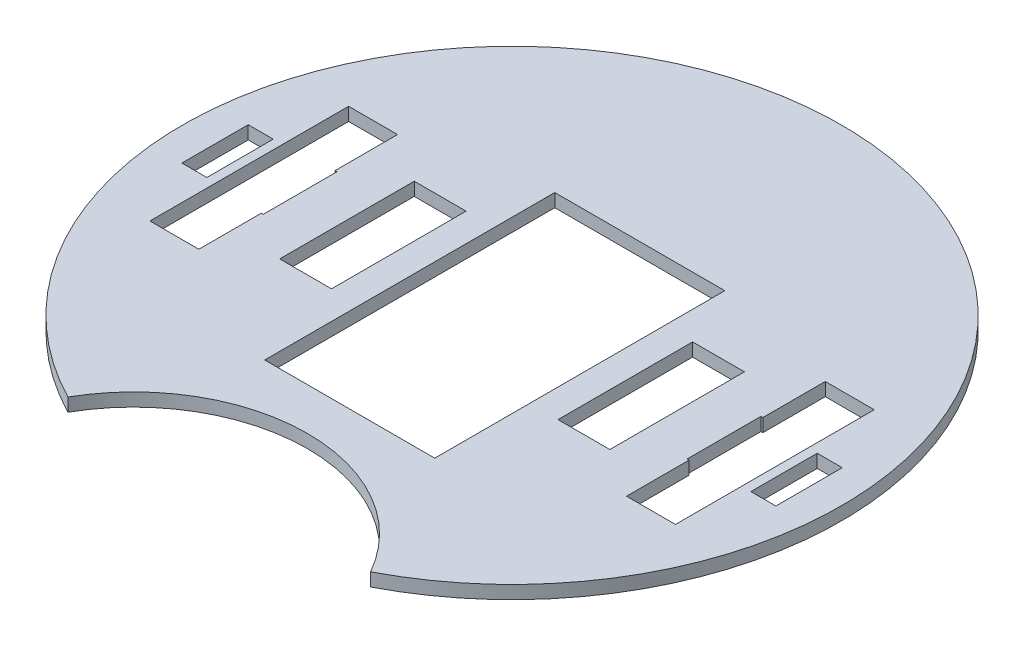
SolidWorks part; units mm, degrees
ref_plane "Front Plane" through (0, 0, 0) normal (0, 0, 1) x (1, 0, 0)
ref_plane "Top Plane" through (0, 0, 0) normal (0, 1, 0) x (1, 0, 0)
ref_plane "Right Plane" through (0, 0, 0) normal (1, 0, 0) x (0, 0, -1)
sketch "Sketch1" plane through (0, 0, 0) normal (0, 1, 0) x (1, 0, 0)
  line L0 (0, -83.2398) -> (-33.2911, -64.4046) construction
  line L1 (0, -83.2398) -> (0, 0) construction
  arc A0 (33.2911, -64.4046) -> (-33.2911, -64.4046) centre (0, 0) ccw
  arc A1 (33.2911, -64.4046) -> (-33.2911, -64.4046) centre (0, -83.2398) ccw
  dimension "D1" = 145
  dimension "D2" = 76.5
  dimension "D3" = 60.5
extrude "Boss-Extrude1" add sketch "Sketch1" along normal blind 2.9
sketch "solenoid placement" plane through (0, 2.9, 0) normal (0, 1, 0) x (1, 0, 0)
  line L0 (0, 0) -> (0, -36) construction
  line L1 (0, -36) -> (0, -44.9898) construction
  line L2 (-19, -36) -> (19, -36) construction
  line L3 (-19, -36) -> (-19, 28.4) construction
  line L4 (-19, 28.4) -> (19, 28.4) construction
  line L5 (19, -36) -> (19, 28.4) construction
  line L6 (-18.7, 28.1) -> (18.7, 28.1)
  line L7 (18.7, -35.7) -> (18.7, 28.1)
  line L8 (-18.7, -35.7) -> (18.7, -35.7)
  line L9 (-18.7, -35.7) -> (-18.7, 28.1)
  circle A1 centre (0, 0) radius 72.5 construction
  arc A2 (33.2911, -64.4046) -> (-33.2911, -64.4046) centre (0, 0) ccw construction
  arc A3 (33.2911, -64.4046) -> (-33.2911, -64.4046) centre (0, -83.2398) ccw construction
  dimension "D1" = 64.4
  dimension "D2" = 36
  dimension "D3" = 0.3
  dimension "D4" = 38
extrude "Cut-Extrude1" cut sketch "solenoid placement" against normal through all
sketch "Sketch2" plane through (0, 2.9, 0) normal (0, 1, 0) x (1, 0, 0)
  line L0 (47.34, -21.5538) -> (47.34, 21.5538) construction
  line L1 (-57.5, -21.5538) -> (-47.34, -21.5538) construction
  line L2 (-57.5, -21.5538) -> (-57.5, 21.5538) construction
  line L3 (-57.5, 21.5538) -> (-47.34, 21.5538) construction
  line L4 (-47.34, -21.5538) -> (-47.34, 21.5538) construction
  line L5 (57.5, 21.5538) -> (47.34, 21.5538) construction
  line L6 (57.5, -21.5538) -> (57.5, 21.5538) construction
  line L7 (57.5, -21.5538) -> (47.34, -21.5538) construction
  line L8 (57.8, -21.8538) -> (57.8, 21.8538)
  line L9 (57.8, -21.8538) -> (47.04, -21.8538)
  line L10 (47.04, -21.8538) -> (47.04, 21.8538)
  line L11 (57.8, 21.8538) -> (47.04, 21.8538)
  line L12 (0, 0) -> (0, 72.5) construction
  line L13 (-57.8, 21.8538) -> (-47.04, 21.8538)
  line L14 (-47.04, -21.8538) -> (-47.04, 21.8538)
  line L15 (-57.8, -21.8538) -> (-47.04, -21.8538)
  line L16 (-57.8, -21.8538) -> (-57.8, 21.8538)
  arc A0 (33.2911, -64.4046) -> (-33.2911, -64.4046) centre (0, 0) ccw construction
extrude "Cut-Extrude2" cut sketch "Sketch2" against normal through all
sketch "Sketch3" plane through (0, 2.9, 0) normal (0, 1, 0) x (1, 0, 0)
  line L0 (-36.31, -14.8) -> (-24.91, -14.8)
  line L1 (-36.51, -15) -> (-24.71, -15) construction
  line L2 (-36.51, -15) -> (-36.51, 15) construction
  line L3 (-36.51, 15) -> (-24.71, 15) construction
  line L4 (-24.71, -15) -> (-24.71, 15) construction
  line L5 (-24.91, -14.8) -> (-24.91, 14.8)
  line L6 (-36.31, 14.8) -> (-24.91, 14.8)
  line L7 (-36.31, -14.8) -> (-36.31, 14.8)
  line L8 (0, 0) -> (0, 72.5) construction
  line L9 (24.71, -15) -> (24.71, 15) construction
  line L10 (36.51, 15) -> (24.71, 15) construction
  line L11 (36.51, -15) -> (36.51, 15) construction
  line L12 (36.51, -15) -> (24.71, -15) construction
  line L13 (36.31, -14.8) -> (36.31, 14.8)
  line L14 (36.31, 14.8) -> (24.91, 14.8)
  line L15 (24.91, -14.8) -> (24.91, 14.8)
  line L16 (36.31, -14.8) -> (24.91, -14.8)
  arc A0 (33.2911, -64.4046) -> (-33.2911, -64.4046) centre (0, 0) ccw construction
  dimension "D1" = 0.2
extrude "Cut-Extrude3" cut sketch "Sketch3" against normal through all
sketch "Sketch5" plane through (0, 2.9, 0) normal (0, 1, 0) x (1, 0, 0)
  line L1 (-65.33, 7.3) -> (-59.83, 7.3)
  line L2 (-65.53, 7.5) -> (-59.63, 7.5) construction
  line L3 (-65.53, 7.5) -> (-65.53, -7.5) construction
  line L4 (-65.53, -7.5) -> (-59.63, -7.5) construction
  line L6 (-59.63, 7.5) -> (-59.63, -7.5) construction
  line L7 (-59.83, 7.3) -> (-59.83, -7.3)
  line L8 (-65.33, -7.3) -> (-59.83, -7.3)
  line L9 (-65.33, 7.3) -> (-65.33, -7.3)
  line L10 (59.63, 7.5) -> (59.63, -7.5) construction
  line L11 (65.53, -7.5) -> (59.63, -7.5) construction
  line L12 (65.53, 7.5) -> (65.53, -7.5) construction
  line L13 (65.53, 7.5) -> (59.63, 7.5) construction
  line L14 (65.33, 7.3) -> (65.33, -7.3)
  line L15 (65.33, -7.3) -> (59.83, -7.3)
  line L28 (0, 0) -> (0, 72.5) construction
  line L29 (59.83, 7.3) -> (59.83, -7.3)
  line L30 (65.33, 7.3) -> (59.83, 7.3)
  arc A0 (33.2911, -64.4046) -> (-33.2911, -64.4046) centre (0, 0) ccw construction
  dimension "D1" = 0.2
extrude "Cut-Extrude4" cut sketch "Sketch5" against normal through all
sketch "Sketch6" plane through (0, 2.9, 0) normal (0, 1, 0) x (1, 0, 0)
  line L0 (-47.04, -21.8538) -> (-47.04, 21.8538) construction
  line L1 (-47.04, 7.8128) -> (-46.91, 7.8128) construction
  line L2 (-47.04, 7.8128) -> (-47.04, -7.8128) construction
  line L3 (-47.04, -7.8128) -> (-46.91, -7.8128) construction
  line L4 (-46.91, 7.8128) -> (-46.91, -7.8128) construction
  line L9 (-47.34, 8.1128) -> (-46.61, 8.1128)
  line L10 (-46.61, 8.1128) -> (-46.61, -8.1128)
  line L11 (-47.34, -8.1128) -> (-46.61, -8.1128)
  line L12 (-47.34, 8.1128) -> (-47.34, -8.1128)
  line L13 (0, 0) -> (0, 72.5) construction
  line L14 (46.91, 7.8128) -> (46.91, -7.8128) construction
  line L15 (47.04, -7.8128) -> (46.91, -7.8128) construction
  line L16 (47.04, 7.8128) -> (47.04, -7.8128) construction
  line L17 (47.04, 7.8128) -> (46.91, 7.8128) construction
  line L18 (47.34, 8.1128) -> (47.34, -8.1128)
  line L19 (47.34, -8.1128) -> (46.61, -8.1128)
  line L20 (46.61, 8.1128) -> (46.61, -8.1128)
  line L21 (47.34, 8.1128) -> (46.61, 8.1128)
  arc A0 (33.2911, -64.4046) -> (-33.2911, -64.4046) centre (0, 0) ccw construction
extrude "Cut-Extrude5" cut sketch "Sketch6" against normal through all
equation "\"smallPulleyTeeth\"= 15"
equation "\"largePulleyTeeth\"= 40"
equation "\"eighthThick\"= 2.9mm"
equation "\"sixteenthThick\" = 1.7mm"
equation "\"quarterThick\"=5.9mm"
equation "\"OD\" = 145mm"
equation "\"puckAngle\" = 60.5deg"
equation "\"D1@Sketch1\"=\"OD\""
equation "\"puckDiam\" = 76.5mm"
equation "\"D2@Sketch1\"=\"puckDiam\""
equation "\"D3@Sketch1\"=\"puckAngle\""
equation "\"D1@Boss-Extrude1\"=\"eighthThick\""
equation "\"axlePress\" = 5.9mm"
equation "\"press\" = 0.2mm"
equation "\"D1@Sketch3\"=\"press\""
equation "\"wheelClear\" = 0.3mm"
equation "\"D1@Sketch2\"=\"wheelClear\""
equation "\"D1@Sketch6\"=\"wheelClear\""
equation "\"D1@Sketch5\"=\"press\""
